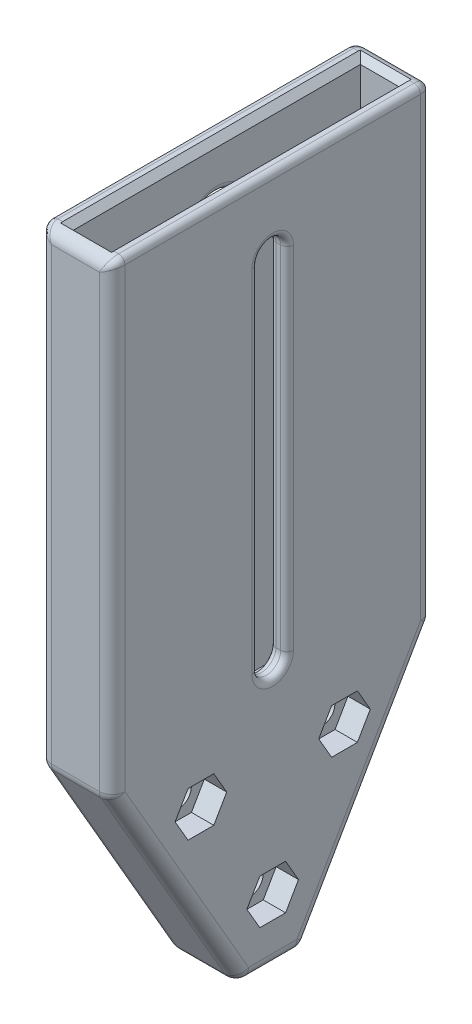
SolidWorks part; units mm, degrees
ref_plane "Front Plane" through (0, 0, 0) normal (0, 0, 1) x (1, 0, 0)
ref_plane "Top Plane" through (0, 0, 0) normal (0, 1, 0) x (1, 0, 0)
ref_plane "Right Plane" through (0, 0, 0) normal (1, 0, 0) x (0, 0, -1)
sketch "Sketch1" plane through (0, 0, 0) normal (1, 0, 0) x (0, 0, -1)
  line L5 (-25.15, 54) -> (-25.15, -19)
  line L6 (-25.15, -19) -> (-4.9427, -54)
  line L7 (-4.9427, -54) -> (4.9427, -54)
  line L8 (0, -54) -> (0, 54) construction
  line L9 (25.15, 54) -> (-25.15, 54)
  line L10 (25.15, -19) -> (4.9427, -54)
  line L11 (25.15, 54) -> (25.15, -19)
  line L12 (0, 42.5) -> (0, -12.5) construction
  line L13 (2.25, 42.5) -> (2.25, -12.5)
  line L14 (-2.25, 42.5) -> (-2.25, -12.5)
  circle A0 centre (0, -44) radius 2
  circle A1 centre (-11.25, -26.5) radius 2
  circle A2 centre (11.25, -26.5) radius 2
  arc A3 (2.25, 42.5) -> (-2.25, 42.5) centre (0, 42.5) ccw
  arc A4 (-2.25, -12.5) -> (2.25, -12.5) centre (0, -12.5) ccw
  point P8 (0, 15)
  dimension "D5" = 4
  dimension "D6" = 11.25
  dimension "D8" = 10
  dimension "D1" = 108
  dimension "D2" = 25.15
  dimension "D3" = 30
  dimension "D4" = 35
  dimension "D7" = 17.5
  dimension "D9" = 55
  dimension "D10" = 4.5
  dimension "D11" = 11.5
extrude "Boss-Extrude1" add sketch "Sketch1" along normal mid plane 11.5
sketch "Sketch2" plane through (0, 54, 0) normal (0, 1, 0) x (1, 0, 0)
  line L11 (-3, -22.5) -> (3, -22.5)
  line L12 (-3, -22.5) -> (-3, 22.5)
  line L13 (-3, 22.5) -> (3, 22.5)
  line L14 (3, -22.5) -> (3, 22.5)
  line L15 (-3, -22.5) -> (3, 22.5) construction
  line L16 (-3, 22.5) -> (3, -22.5) construction
  point P12 (0, 0)
  dimension "D1" = 45
  dimension "D2" = 6
extrude "Cut-Extrude1" cut sketch "Sketch2" against normal blind 75
sketch "Sketch3" plane through (5.75, 0, 0) normal (1, 0, 0) x (0, 0, -1)
  line L0 (-4.9427, -54) -> (4.9427, -54) construction
  line L1 (-7.2085, -26.5) -> (-9.2293, -23)
  line L2 (-9.2293, -23) -> (-13.2707, -23)
  line L3 (-13.2707, -23) -> (-15.2915, -26.5)
  line L4 (-15.2915, -26.5) -> (-13.2707, -30)
  line L5 (-13.2707, -30) -> (-9.2293, -30)
  line L6 (-9.2293, -30) -> (-7.2085, -26.5)
  line L7 (13.2707, -30) -> (15.2915, -26.5)
  line L8 (15.2915, -26.5) -> (13.2707, -23)
  line L9 (13.2707, -23) -> (9.2293, -23)
  line L10 (9.2293, -23) -> (7.2085, -26.5)
  line L11 (7.2085, -26.5) -> (9.2293, -30)
  line L12 (9.2293, -30) -> (13.2707, -30)
  line L13 (2.0207, -47.5) -> (4.0415, -44)
  line L14 (4.0415, -44) -> (2.0207, -40.5)
  line L15 (2.0207, -40.5) -> (-2.0207, -40.5)
  line L16 (-2.0207, -40.5) -> (-4.0415, -44)
  line L17 (-4.0415, -44) -> (-2.0207, -47.5)
  line L18 (-2.0207, -47.5) -> (2.0207, -47.5)
  circle A0 centre (-11.25, -26.5) radius 3.5 construction
  circle A1 centre (11.25, -26.5) radius 3.5 construction
  circle A2 centre (0, -44) radius 3.5 construction
  dimension "D1" = 7
extrude "Cut-Extrude2" cut sketch "Sketch3" against normal blind 3.5
sketch "Sketch4" plane through (-5.75, 0, 0) normal (-1, 0, 0) x (0, 0, 1)
  line L0 (0, 42.5) -> (0, -12.5) construction
  line L1 (4.25, 42.5) -> (4.25, -12.5)
  line L2 (-4.25, 42.5) -> (-4.25, -12.5)
  arc A0 (4.25, 42.5) -> (-4.25, 42.5) centre (0, 42.5) ccw
  arc A1 (-4.25, -12.5) -> (4.25, -12.5) centre (0, -12.5) ccw
  point P4 (0, 15)
  dimension "D1" = 8.5
extrude "Cut-Extrude3" cut sketch "Sketch4" against normal up to surface (2.75 mm away) up to face at (-3, 15, 0)
chamfer "Chamfer1" distance 1 angle 45 4 edges at (0, 54, -22.5) (3, 54, 0) (0, 54, 22.5) (-3, 54, 0)
fillet "Fillet1" radius 2 16 edges at (5.75, 17.5, -25.15) (0, 54, -25.15) (-5.75, 17.5, -25.15) (5.75, -36.5, -15.0464) (0, -19, -25.15) (-5.75, -36.5, -15.0464) (5.75, -54, 0) (0, -54, -4.9427) (-5.75, -54, 0) (5.75, -36.5, 15.0464) (0, -54, 4.9427) (-5.75, -36.5, 15.0464) (0, 54, 25.15) (5.75, 17.5, 25.15) (0, -19, 25.15) (-5.75, 17.5, 25.15)
fillet "Fillet2" radius 1 22 edges at (-5.75, -16.75, 0) (-5.75, 15, -4.25) (-5.75, 46.75, 0) (-3, 46.75, 0) (-3, 15, -4.25) (-3, -16.75, 0) (5.75, 44.75, 0) (5.75, 15, -2.25) (5.75, -14.75, 0) (3, 44.75, 0) (3, 15, -2.25) (3, -14.75, 0) (-5.1642, 53.4142, -24.5642) (-5.1642, 53.4142, 24.5642) (5.1642, 53.4142, -24.5642) (5.1642, 53.4142, 24.5642) (-5.75, 15, 4.25) (-3, 15, 4.25) (5.75, 15, 2.25) (3, 15, 2.25) (-5.75, 54, 0) (5.75, 54, 0)
